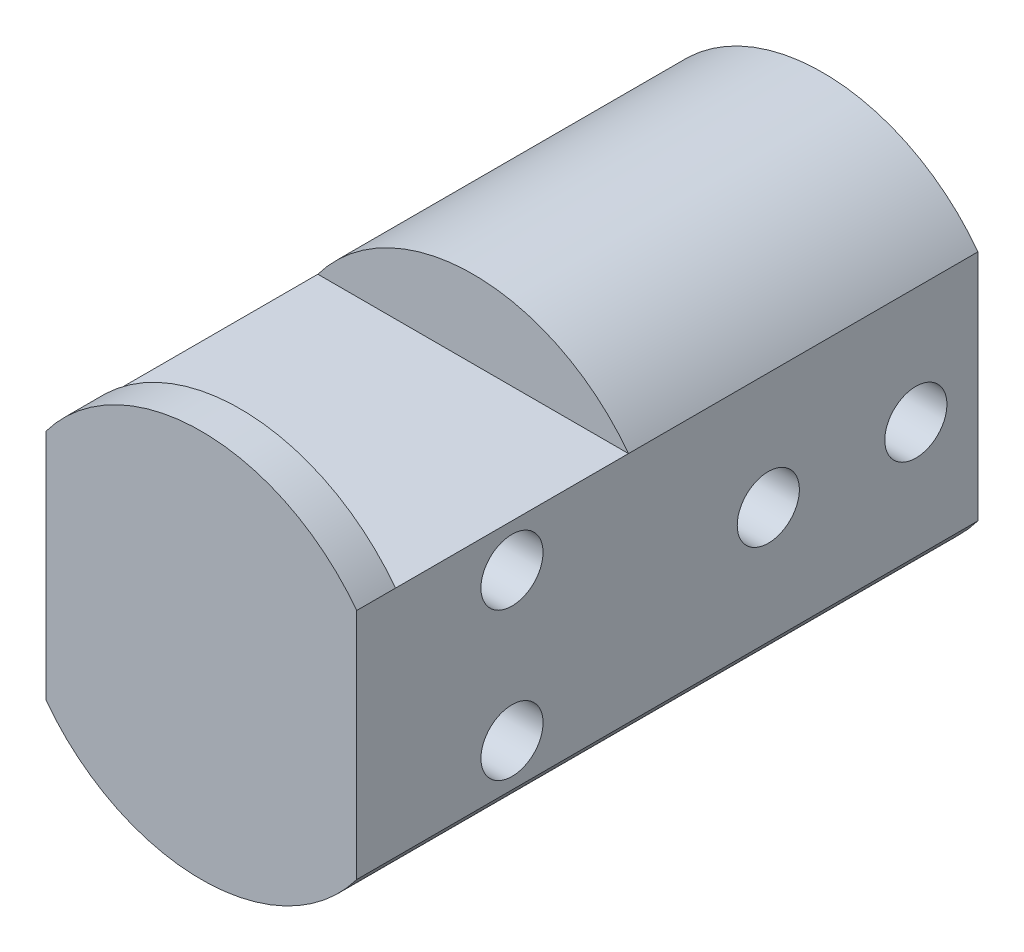
SolidWorks part; units mm, degrees
material "AISI 1045 钢，冷拔"
ref_plane "前视" through (0, 0, 0) normal (0, 0, 1) x (1, 0, 0)
ref_plane "上视" through (0, 0, 0) normal (0, 1, 0) x (1, 0, 0)
ref_plane "右视" through (0, 0, 0) normal (1, 0, 0) x (0, 0, -1)
sketch "草图1" plane through (0, 0, 0) normal (0, 0, 1) x (1, 0, 0)
  line L0 (-20, -15) -> (-20, 15)
  line L1 (20, 15) -> (20, -15)
  circle A0 centre (0, 0) radius 25
  dimension "D1" = 50
  dimension "D2" = 20
extrude "凸台-拉伸1" add sketch "草图1" along normal blind 80 contours L1 A0 L0 region at (0, 0, 0)
sketch "草图2" plane through (0, 0, 0) normal (0, 0, -1) x (-1, 0, 0)
  line L1 (7.5, -7.5) -> (-7.5, -7.5)
  line L2 (7.5, -7.5) -> (7.5, 7.5)
  line L3 (7.5, 7.5) -> (-7.5, 7.5)
  line L4 (-7.5, -7.5) -> (-7.5, 7.5)
  line L5 (7.5, -7.5) -> (-7.5, 7.5) construction
  line L6 (7.5, 7.5) -> (-7.5, -7.5) construction
  point P0 (0, 0)
  dimension "D1" = 15
  dimension "D2" = 15
extrude "切除-拉伸1" cut sketch "草图2" against normal blind 35
sketch "草图3" plane through (-20, 0, 0) normal (-1, 0, 0) x (0, 0, 1)
  line L0 (0, -15) -> (0, 15) construction
  line L1 (80, -15) -> (80, 15) construction
  line L2 (80, 0) -> (49.5816, 0) construction
  circle A0 centre (8, 0) radius 4
  circle A1 centre (27, 0) radius 4
  circle A2 centre (60, 9.5) radius 4
  circle A3 centre (60, -9.5) radius 4
  dimension "D3" = 8
  dimension "D1" = 8
  dimension "D4" = 19
  dimension "D7" = 20
  dimension "D8" = 19
extrude "切除-拉伸2" cut sketch "草图3" against normal through all
sketch "草图6" plane through (0, 0, 80) normal (0, 0, 1) x (1, 0, 0)
  line L0 (-20, 15) -> (20, 15)
  arc A0 (20, 15) -> (-20, 15) centre (0, 0) ccw
extrude "切除-拉伸4" cut sketch "草图6" against normal blind 35
fillet "圆角1" radius 1 4 edges at (-7.5, -7.5, 17.5) (7.5, -7.5, 17.5) (-7.5, 7.5, 17.5) (7.5, 7.5, 17.5)
extrude "凸台-拉伸2" add sketch "草图6<2>" against normal blind 5
sketch "草图6<2>" plane through (0, 0, 80) normal (0, 0, 1) x (1, 0, 0) same geometry as "草图6"
